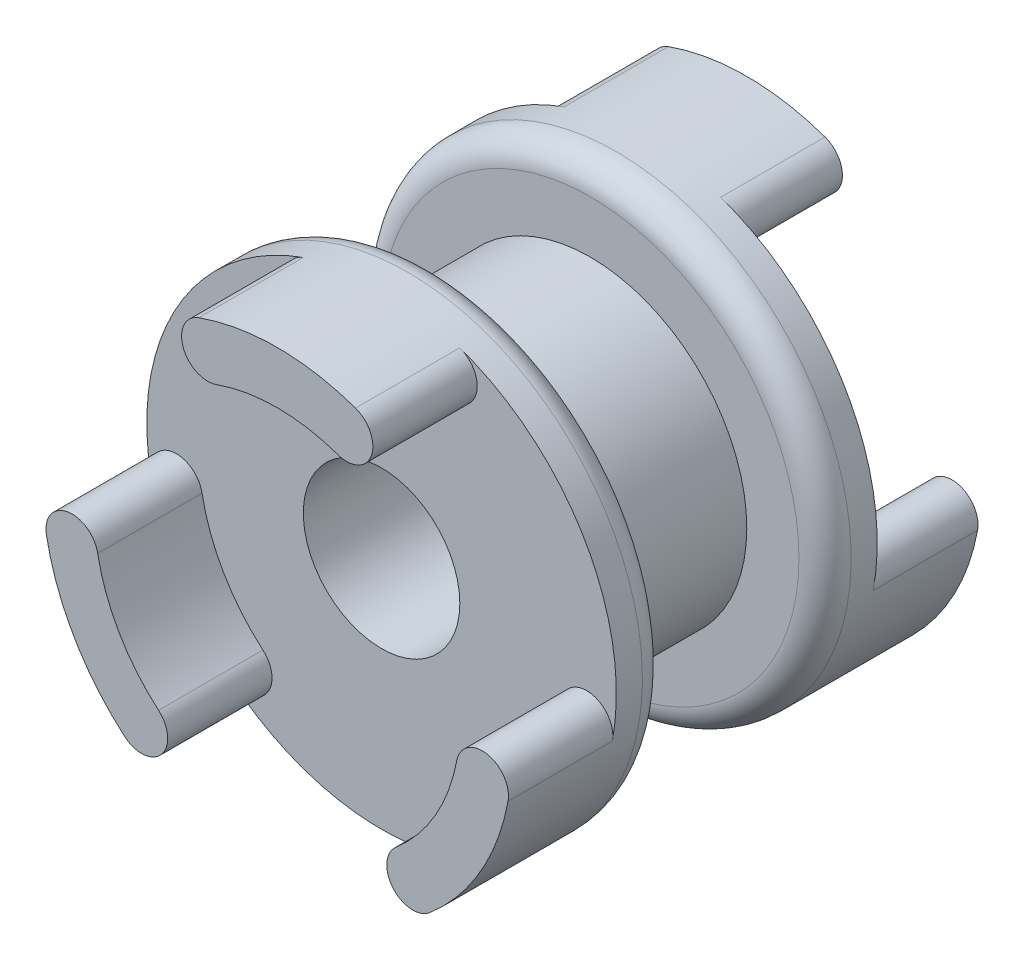
SolidWorks part; units mm, degrees
ref_plane "Front Plane" through (0, 0, 0) normal (0, 0, 1) x (1, 0, 0)
ref_plane "Top Plane" through (0, 0, 0) normal (0, 1, 0) x (1, 0, 0)
ref_plane "Right Plane" through (0, 0, 0) normal (1, 0, 0) x (0, 0, -1)
sketch "Sketch2" plane through (0, 0, 0) normal (1, 0, 0) x (0, 0, -1)
  line L0 (-5, 3) -> (-5, 9)
  line L1 (-5, 9) -> (-3, 9)
  line L2 (-3, 9) -> (-3, 6)
  line L3 (-3, 6) -> (3, 6)
  line L4 (0, -20.9183) -> (0, 20.9183) construction
  line L5 (-5, 3) -> (5, 3)
  line L6 (3, 9) -> (3, 6)
  line L7 (5, 9) -> (3, 9)
  line L8 (5, 3) -> (5, 9)
  line L9 (0, 0) -> (15.424, 0)
  point P10 (0, 0)
  point P13 (0, 3)
  point P14 (0, 6)
  dimension "D1" = 6
  dimension "D2" = 3
  dimension "D3" = 6
  dimension "D4" = 2
  dimension "D5" = 3
revolve "Revolve1" add sketch "Sketch2" angle 360 about L9 region at (0, 5.3571, 2.9286) region at (0, 5.3571, -2.9286)
fillet "Fillet2" radius 1 2 edges at (9, 0, -3) (9, 0, 3)
sketch "Sketch3" plane through (0, 0, -5) normal (0, 0, -1) x (-1, 0, 0)
  line L0 (0, 0) -> (0, 18.3802) construction
  line L1 (0, 55) -> (0, -55) construction
  line L2 (3, 8.4853) -> (2.3333, 6.5997) construction
  arc A0 (0, 9) -> (3, 8.4853) centre (0, 0) cw
  arc A1 (0, 7) -> (2.3333, 6.5997) centre (0, 0) cw
  circle A2 centre (2.6667, 7.5425) radius 1
  arc A3 (0, 7) -> (-2.3333, 6.5997) centre (0, 0) ccw
  arc A4 (0, 9) -> (-3, 8.4853) centre (0, 0) ccw
  circle A5 centre (-2.6667, 7.5425) radius 1
  dimension "D1" = 9
  dimension "D2" = 3
  dimension "D3" = 2
extrude "Boss-Extrude1" add sketch "Sketch3" along normal blind 4 contours A4 A5 A3 A1 A2 A0 | A5 | A2 region at (0, 7.9706, -5) region at (-2.6667, 7.5425, -5) region at (2.6667, 7.5425, -5)
pattern_circular "CirPattern1" count 3 over 360 about axis through (0, 0, -5) along (0, 0, 1) of "Boss-Extrude1"
mirror "Mirror1" about plane through (0, 0, 0) normal (0, 0, 1) of "CirPattern1"
